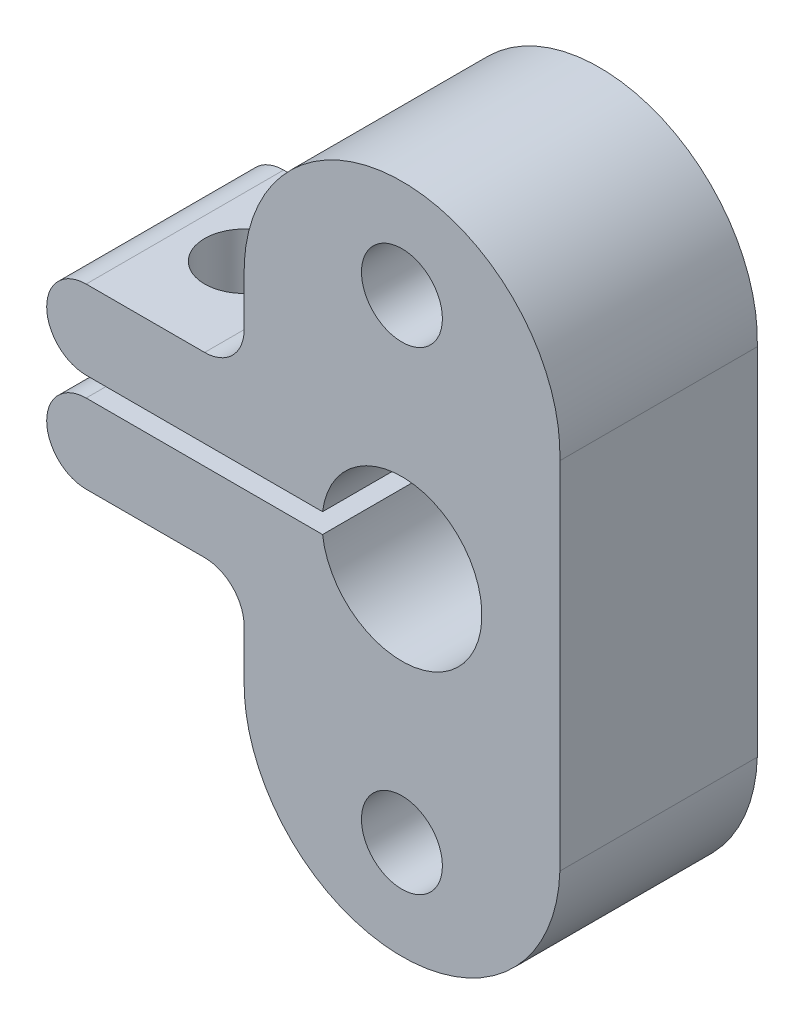
SolidWorks part; units mm, degrees
ref_plane "Plano frontal" through (0, 0, 0) normal (0, 0, 1) x (1, 0, 0)
ref_plane "Plano superior" through (0, 0, 0) normal (0, 1, 0) x (1, 0, 0)
ref_plane "Plano direito" through (0, 0, 0) normal (1, 0, 0) x (0, 0, -1)
sketch "Esboço1" plane through (0, 0, 0) normal (0, 0, 1) x (1, 0, 0)
  line L0 (0.004, -9.0015) -> (0.004, 9.0015) construction
  line L1 (-7.992, -8.75) -> (-7.992, -4.5)
  line L2 (8, -9.253) -> (8, 8.747)
  line L3 (0, 0) -> (-20, 0) construction
  line L4 (-8, -0.5) -> (-17.992, -0.5)
  line L5 (-17.992, -0.5) -> (-17.992, -4.5)
  line L6 (-17.992, -4.5) -> (-7.992, -4.5)
  line L7 (-8, -0.5) -> (-4.019, -0.5)
  line L8 (-8, 0.5) -> (-4.019, 0.5)
  line L9 (-8, 0.5) -> (-17.992, 0.5)
  line L10 (-17.992, 0.5) -> (-17.992, 4.5)
  line L11 (-17.992, 4.5) -> (-7.992, 4.5)
  line L12 (-7.992, 4.5) -> (-7.992, 8.75)
  arc A0 (-4.019, -0.5) -> (-4.019, 0.5) centre (0, 0) ccw
  arc A1 (-7.992, -8.75) -> (8, -9.253) centre (0.004, -9.0015) ccw
  arc A2 (8, 8.747) -> (-7.992, 8.75) centre (0.004, 9.0015) ccw
  circle A3 centre (0, 12) radius 2.05
  circle A4 centre (0, -12) radius 2.05
  point P1 (0.0055, 17.0015)
  point P5 (0, 0)
  point P25 (-0.2475, -16.9976)
  point P26 (0, 0)
  dimension "D1" = 8.1
  dimension "D3" = 8
  dimension "D4" = 4.1
  dimension "D5" = 12
  dimension "D6" = 12
  dimension "D14" = 8
  dimension "D2" = 18
  dimension "D7" = 20
  dimension "D8" = 4
  dimension "D9" = 0.5
  dimension "D10" = 10
  dimension "D11" = 34
  dimension "D12" = 16
  dimension "D13" = 4.25
extrude "Ressalto-extrusão1" add sketch "Esboço1" along normal blind 10
sketch "Esboço2" plane through (0, -4.5, 0) normal (0, -1, 0) x (1, 0, 0)
  line L0 (-17.992, 10) -> (-17.992, 0) construction
  line L1 (-7.992, 0) -> (-17.992, 0) construction
  circle A0 centre (-12.992, 5) radius 2
  dimension "D1" = 4
  dimension "D2" = 5
  dimension "D3" = 5
extrude "Corte-extrusão1" cut sketch "Esboço2" against normal up to surface (9 mm away) up to face at (-12.992, 4.5, 5)
fillet "Filete1" radius 2 6 edges at (-7.992, -4.5, 5) (-7.992, 4.5, 5) (-17.992, -4.5, 5) (-17.992, 0.5, 5) (-17.992, -0.5, 5) (-17.992, 4.5, 5)
